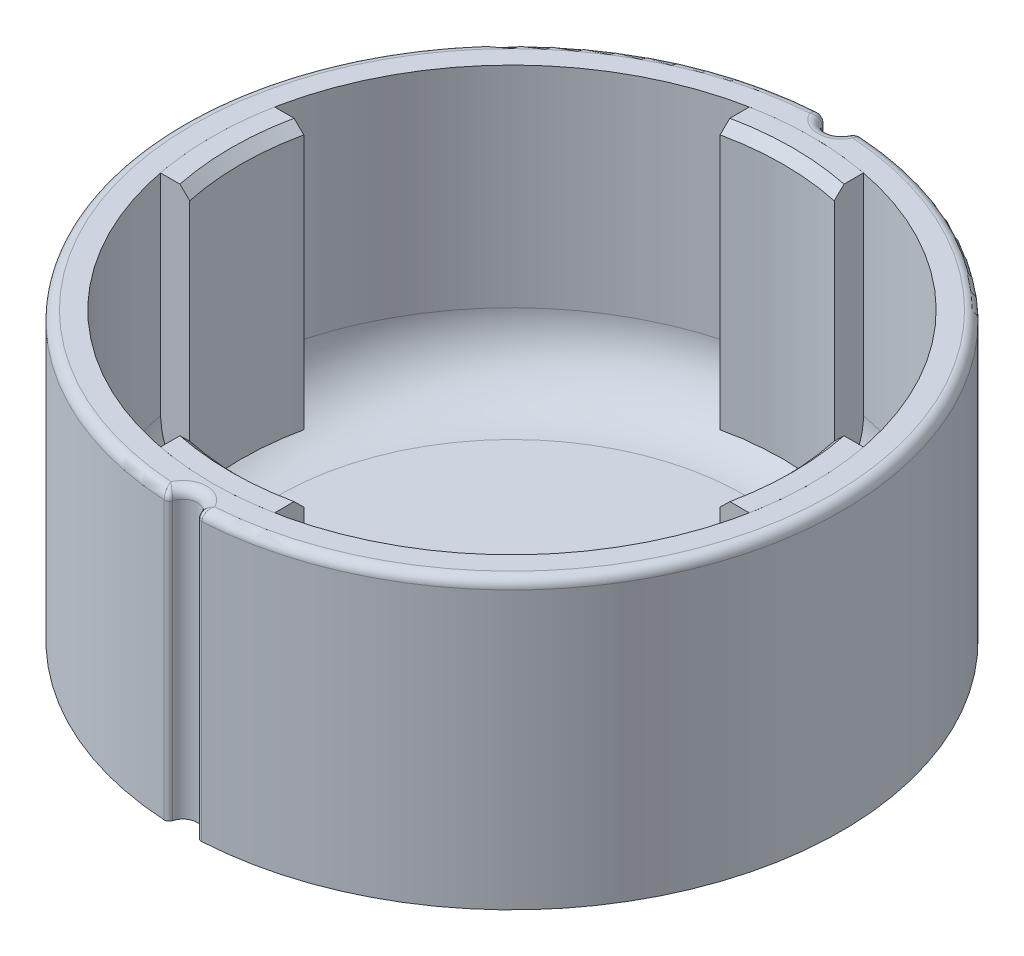
SolidWorks part; units mm, degrees
other "Markup1"
sketch "Sketch4" plane through (-34.5, 25, 34.4428) normal (-0.055, 0.9636, 0.2616) x (0.9976, 0.0639, -0.0258)
other "Markup5"
sketch "Sketch8" plane through (34.5, 25, 34.4428) normal (0.0041, 0.9851, 0.1719) x (0.981, -0.0374, 0.1906)
other "Markup6"
sketch "Sketch9" plane through (34.5, 25, 34.4428) normal (0.0041, 0.9851, 0.1719) x (0.981, -0.0374, 0.1906)
other "Markup7"
sketch "Sketch10" plane through (-34.5, 25, 34.4428) normal (-0.125, 0.9874, 0.0969) x (0.5933, -0.0039, 0.805)
ref_plane "Front Plane" through (0, 0, 0) normal (0, 0, 1) x (1, 0, 0)
ref_plane "Top Plane" through (0, 0, 0) normal (0, 1, 0) x (1, 0, 0)
ref_plane "Right Plane" through (0, 0, 0) normal (1, 0, 0) x (0, 0, -1)
sketch "Sketch1" plane through (0, 0, 0) normal (0, 1, 0) x (1, 0, 0)
  line L3 (0, 0.002) -> (0, 3.7877) construction
  line L4 (0, 3.7877) -> (2.417, 3.7877)
  line L5 (0, 3.7877) -> (-2.417, 3.7877)
  arc A0 (1.9642, -34.442) -> (34.1982, 4.5552) centre (0, 0.002) ccw
  arc A2 (-2.417, 3.7877) -> (2.417, 3.7877) centre (0, 0.002) ccw
  circle A3 centre (0, 0.002) radius 34.5 construction
  arc A7 (-1.3541, 33.8562) -> (1.3541, 33.8562) centre (0, 34.5015) ccw
  arc A8 (34.1982, 4.5552) -> (2.3241, 34.4236) centre (0, 0.002) ccw
  arc A9 (-2.3241, 34.4236) -> (-34.1982, 4.5552) centre (0, 0.002) ccw
  arc A10 (-34.1982, 4.5552) -> (-1.9642, -34.442) centre (0, 0.002) ccw
  arc A11 (1.3541, 33.8562) -> (2.3241, 34.4236) centre (2.2568, 33.4259) cw
  arc A12 (-1.3541, 33.8562) -> (-2.3241, 34.4236) centre (-2.2568, 33.4259) ccw
  arc A13 (1.4518, -34.0686) -> (-1.4518, -34.0686) centre (0, -34.4457) ccw
  arc A14 (1.4518, -34.0686) -> (1.9642, -34.442) centre (1.9358, -33.9428) ccw
  arc A15 (-1.4518, -34.0686) -> (-1.9642, -34.442) centre (-1.9358, -33.9428) cw
  point P15 (1.4997, 34.4694)
  dimension "D2" = 4.834
  dimension "D3" = 4.4915
  dimension "D4" = 34.5
  dimension "D5" = 1
  dimension "D6" = 1.5
  dimension "D7" = 0.5
  dimension "D11" = 1.4997
sketch "Sketch2" plane through (0, 0, 0) normal (0, 1, 0) x (1, 0, 0)
  line L0 (0, 31.4) -> (0, 28.4) construction
  line L1 (-5.9726, 30.8268) -> (0, 31.4) construction
  line L2 (0, 31.4) -> (5.9726, 30.8268) construction
  line L3 (-5.9726, 30.8268) -> (-5.9726, 27.7649)
  line L6 (5.9726, 27.7649) -> (5.9726, 30.8268)
  circle A16 centre (0, 0) radius 31.4
  arc A18 (-5.9726, 27.7649) -> (5.9726, 27.7649) centre (0, 0) cw
  point P3 (0, 28.4)
  dimension "D1" = 62.8
  dimension "D2" = 6
  dimension "D3" = 3
extrude "Boss-Extrude1" add sketch "Sketch1" along normal blind 30 contours A10 A0 A8 A7 A9 A2 L5 L4 | L5 A2 L4 region at (0, 0, 0.1522) region at (2.2155, 0, 33.5591)
extrude "Cut-Extrude2" cut sketch "Sketch2" along normal up to next from offset 1 contours A16 | A16 region at (0, 0, 0.35)
extrude "Boss-Extrude2" add sketch "Sketch2<2>" along normal up to surface (30 mm away) separate body contours A16 region at (0, 0, -29.6983) up to face at (0, 30, 31.4)
sketch "Sketch2<2>" plane through (0, 0, 0) normal (0, 1, 0) x (1, 0, 0) same geometry as "Sketch2"
chamfer "Chamfer2" distance 1 angle 45 1 edges at (0, 30, -28.4)
pattern_circular "CirPattern2" count 4 over 360 about axis through (0, 30, 0) along (0, 1, 0) of bodies 106
fillet "Fillet1" radius 1 8 edges at (-1.7518, 30, -34.2891) (0, 30, -33.0015) (1.7518, 30, -34.2891) (34.4995, 30, 0.1783) (1.6412, 30, 34.3469) (0, 30, 32.9457) (-1.6412, 30, 34.3469) (-34.4995, 30, 0.1783)
fillet "Fillet2" radius 7 1 edges at (0, 1, 31.4)
